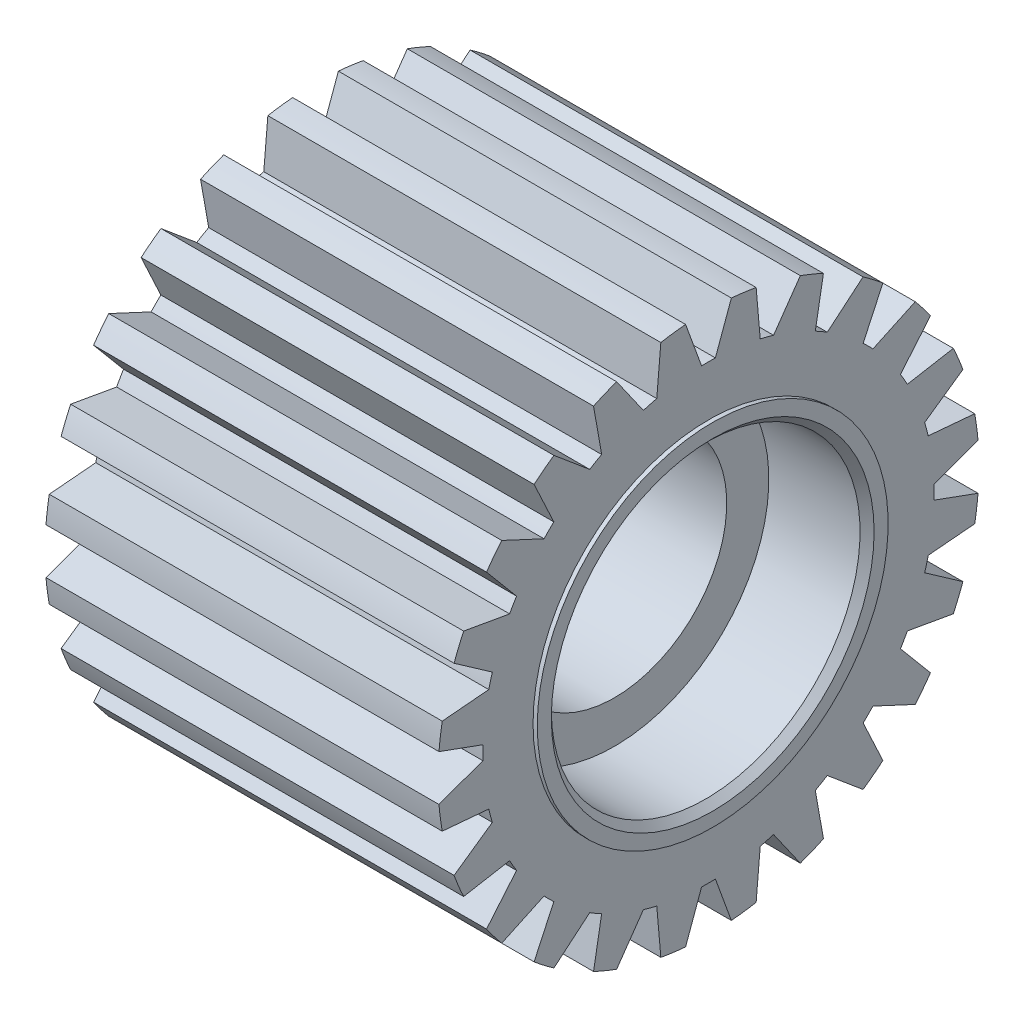
SolidWorks part; units mm, degrees
material "1.7131 (16MnCr5)"
ref_plane "Vorne" through (0, 0, 0) normal (0, 0, 1) x (1, 0, 0)
ref_plane "Oben" through (0, 0, 0) normal (0, 1, 0) x (1, 0, 0)
ref_plane "Rechts" through (0, 0, 0) normal (1, 0, 0) x (0, 0, -1)
ref_axis "Achse1" through (-15.73, 0, 0) along (1, 0, 0)
sketch "Skizze1" plane through (0, 0, 0) normal (0, 0, 1) x (1, 0, 0)
  line L0 (-36.0104, 0) -> (46.5768, 0) construction
  line L1 (-14.3, 12.5) -> (-14.3, 11.5)
  line L2 (-13.8, 11) -> (-7.3, 11)
  line L3 (-7.3, 11) -> (-7.3, 8)
  line L4 (-7.3, 8) -> (7.3, 8)
  line L5 (7.3, 8) -> (7.3, 11)
  line L6 (7.3, 11) -> (13.8, 11)
  line L7 (14.3, 11.5) -> (14.3, 12.5)
  line L8 (14.3, 12.5) -> (14, 12.5)
  line L9 (14, 12.5) -> (14, 19.2715)
  line L10 (14, 19.2715) -> (-14, 19.2715)
  line L11 (-14, 19.2715) -> (-14, 12.5)
  line L12 (-14, 12.5) -> (-14.3, 12.5)
  line L13 (0, 0) -> (0, 20) construction
  line L16 (-14.3, 11.5) -> (-13.8, 11)
  line L17 (13.8, 11) -> (14.3, 11.5)
  point P4 (-14.3, 11)
  point P5 (14.3, 11)
  point P8 (0, 8)
  dimension "D1" = 22
  dimension "D2" = 7
  dimension "D3" = 16
  dimension "D4" = 28.6
  dimension "D5" = 38.543
  dimension "D6" = 25
  dimension "D7" = 28
revolve "Rotation1" add sketch "Skizze1" angle 360 about L0
sketch "Skizze2" plane through (14, 0, 0) normal (1, 0, 0) x (0, 0, -1)
  line L0 (0, 0) -> (0, 74.3665) construction
  line L1 (0.4919, 16.0765) -> (1.6297, 19.2025)
  line L2 (-0.4919, 16.0765) -> (-1.6297, 19.2025)
  circle A0 centre (0, 0) radius 16.084 construction
  circle A1 centre (0, 0) radius 18 construction
  circle A2 centre (0, 0) radius 19.2715 construction
  arc A3 (0.4919, 16.0765) -> (-0.4919, 16.0765) centre (0, 0) ccw
  arc A4 (1.6297, 19.2025) -> (-1.6297, 19.2025) centre (0, 0) ccw
  point P10 (1.178, 17.9614)
  point P11 (-1.178, 17.9614)
  dimension "D1" = 32.168
  dimension "D2" = 36
  dimension "D3" = 38.543
  dimension "D4" = 20
  dimension "D5" = 2.356
extrude "Schnitt-Linear austragen1" cut sketch "Skizze2" against normal up to next
pattern_circular "Kreismuster1" count 24 over 360 about axis through (-15.73, 0, 0) along (1, 0, 0) of "Schnitt-Linear austragen1"
sketch "Skizze3" plane through (14.3, 0, 0) normal (1, 0, 0) x (0, 0, -1)
  circle A0 centre (0, 0) radius 18 construction
  dimension "D1" = 36
sketch "Skizze4" plane through (0, 0, 0) normal (1, 0, 0) x (0, 0, -1)
  line L1 (-3, 8) -> (3, 8)
  line L2 (-3, 8) -> (-3, 11.15)
  line L3 (-2.75, 11.4) -> (2.75, 11.4)
  line L4 (3, 8) -> (3, 11.15)
  arc A0 (2.75, 11.4) -> (3, 11.15) centre (2.75, 11.15) cw
  arc A1 (-2.75, 11.4) -> (-3, 11.15) centre (-2.75, 11.15) ccw
  point P4 (0, 8)
  dimension "D4" = 0.25
  dimension "D1" = 8
  dimension "D2" = 11.4
  dimension "D3" = 6
extrude "Schnitt-Linear austragen2" [suppressed] cut sketch "Skizze4" against normal mid plane 40
